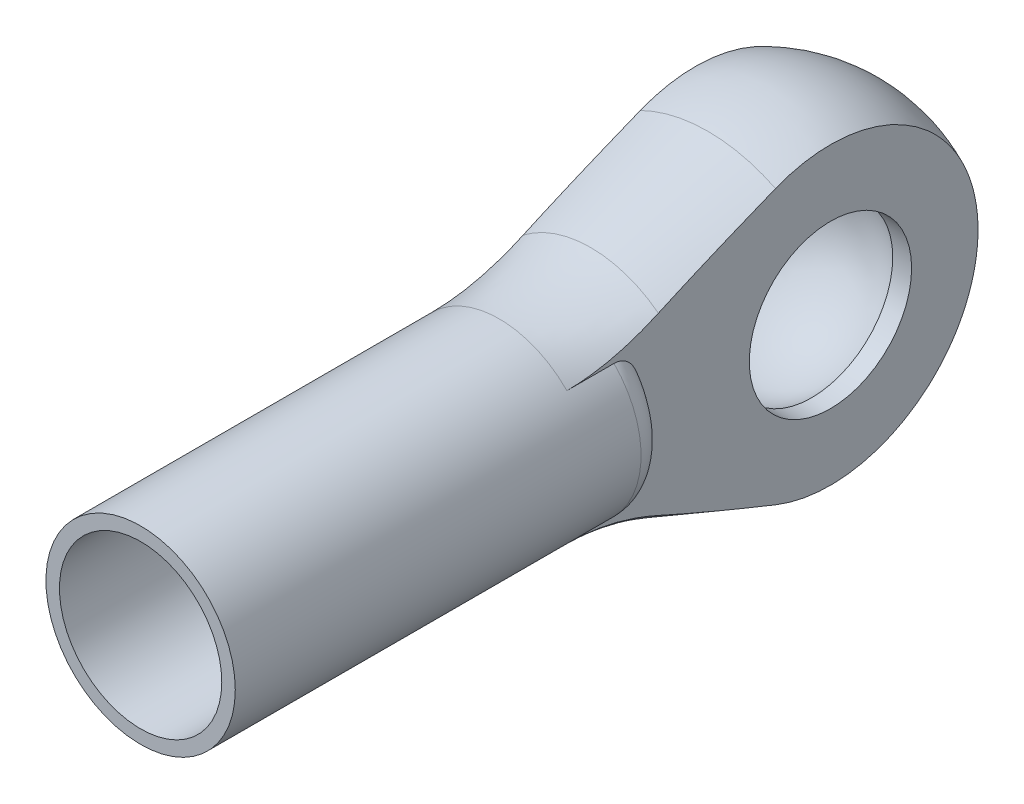
SolidWorks part; units mm, degrees
material "ABS"
ref_plane "Front Plane" through (0, 0, 0) normal (0, 0, 1) x (1, 0, 0)
ref_plane "Top Plane" through (0, 0, 0) normal (0, 1, 0) x (1, 0, 0)
ref_plane "Right Plane" through (0, 0, 0) normal (1, 0, 0) x (0, 0, -1)
sketch "Sketch1" plane through (0, 0, 0) normal (1, 0, 0) x (0, 0, -1)
  line L0 (0, 0) -> (14, 0) construction
  line L1 (0, 3.5) -> (5.9702, 5.6462)
  line L2 (0, 3.5) -> (0, 0)
  arc A0 (14, 0) -> (5.9702, 5.6462) centre (8, 0) ccw
  arc A1 (11.5, 0) -> (4.5, 0) centre (8, 0) ccw
  dimension "D1" = 7
  dimension "D2" = 12
  dimension "D3" = 3.5
  dimension "D4" = 0
  dimension "D5" = 14
revolve "Revolve1" add sketch "Sketch1" angle 360 about L0 region at (0, 1.75, -0.1523)
sketch "Sketch2" plane through (0, 0, 0) normal (0, 1, 0) x (1, 0, 0)
  line L0 (0, 0) -> (0, 14) construction
  line L2 (-2.5, -14) -> (2.5, -14)
  line L3 (-2.5, -14) -> (-2.5, 14)
  line L4 (-2.5, 14) -> (2.5, 14)
  line L5 (2.5, -14) -> (2.5, 14)
  line L6 (-2.5, -14) -> (2.5, 14) construction
  line L7 (-2.5, 14) -> (2.5, -14) construction
  line L8 (7.12, -0.7489) -> (-6.2655, -0.7489)
  line L9 (7.12, -0.7489) -> (7.12, 14)
  line L10 (7.12, 14) -> (-6.2655, 14)
  line L11 (-6.2655, -0.7489) -> (-6.2655, 14)
  arc A0 (5.6462, 5.9702) -> (-5.6462, 5.9702) centre (0, 8) ccw construction
  dimension "D1" = 5
extrude "Cut-Extrude1" cut sketch "Sketch2" against normal mid plane 35 contours L11 L8 L3 L10 | L9 L10 L5 L8 region at (-4.3828, 0, -6.6255) region at (4.81, 0, -6.6255)
chamfer "Chamfer1" distance 0.5 angle 45 2 edges at (2.5, 0, -10.4495) (-2.5, 0, -10.4495) first distance on face at (2.5, -0.6533, -4.8561) first distance on face at (-2.5, 0, -10.4495)
sketch "Sketch3" plane through (2.5, 0, 0) normal (1, 0, 0) x (0, 0, -1)
  circle A0 centre (8, 0) radius 3
  dimension "D1" = 6
extrude "Cut-Extrude2" cut sketch "Sketch3" against normal blind 35
sketch "Sketch4" plane through (0, 0, 0) normal (0, 0, 1) x (1, 0, 0)
  circle A0 centre (0, 0) radius 3.5
  circle A1 centre (0, 0) radius 3
  dimension "D1" = 6
  dimension "D2" = 7
extrude "Boss-Extrude1" add sketch "Sketch4" along normal blind 15
sketch "Sketch5" plane through (0, 0, 0) normal (0, 0, 1) x (1, 0, 0)
  line L4 (2.5, -1.6583) -> (2.5, 1.6583)
  line L5 (-2.5, 1.6583) -> (-2.5, -1.6583)
  line L6 (2.5, -1.6583) -> (2.5, 1.6583)
  line L7 (-2.5, 1.6583) -> (-2.5, -1.6583)
  arc A4 (2.5, 1.6583) -> (-2.5, 1.6583) centre (0, 0) ccw
  arc A5 (-2.5, -1.6583) -> (2.5, -1.6583) centre (0, 0) ccw
  arc A6 (2.5, 1.6583) -> (-2.5, 1.6583) centre (0, 0) ccw
  arc A7 (-2.5, -1.6583) -> (2.5, -1.6583) centre (0, 0) ccw
  circle A8 centre (0, 0) radius 3
  circle A9 centre (0, 0) radius 3
  line M6 (2.5, -1.6583) -> (2.5, 1.6583)
  arc M7 (2.5, 1.6583) -> (-2.5, 1.6583) centre (0, 0) ccw
  line M8 (-2.5, 1.6583) -> (-2.5, -1.6583)
  arc M9 (-2.5, -1.6583) -> (2.5, -1.6583) centre (0, 0) ccw
  dimension "D1" = 0
  dimension "D2" = 0
extrude "Boss-Extrude2" add sketch "Sketch5" along normal blind 1 contours A9 M6 | M9 M6 M7 M8 | A9 M8 region at (0, 0, 0) region at (2.7015, 0, 0) region at (-2.7015, 0, 0)
extrude "Boss-Extrude3" add sketch "Sketch4<2>" against normal blind 1
sketch "Sketch4<2>" plane through (0, 0, 0) normal (0, 0, 1) x (1, 0, 0) same geometry as "Sketch4"
extrude "Boss-Extrude4" add sketch "Sketch5<4>" against normal blind 1 contours A9 M6 | A9 M8 region at (2.7015, 0, 0) region at (-2.7015, 0, 0)
sketch "Sketch5<4>" plane through (0, 0, 0) normal (0, 0, 1) x (1, 0, 0) same geometry as "Sketch5"
fillet "Fillet1" radius 1 2 edges at (-3.5, 0, -1) (3.5, 0, -1)
fillet "Fillet2" radius 10 2 edges at (0, -3.5, 0) (0, 3.5, 0)
